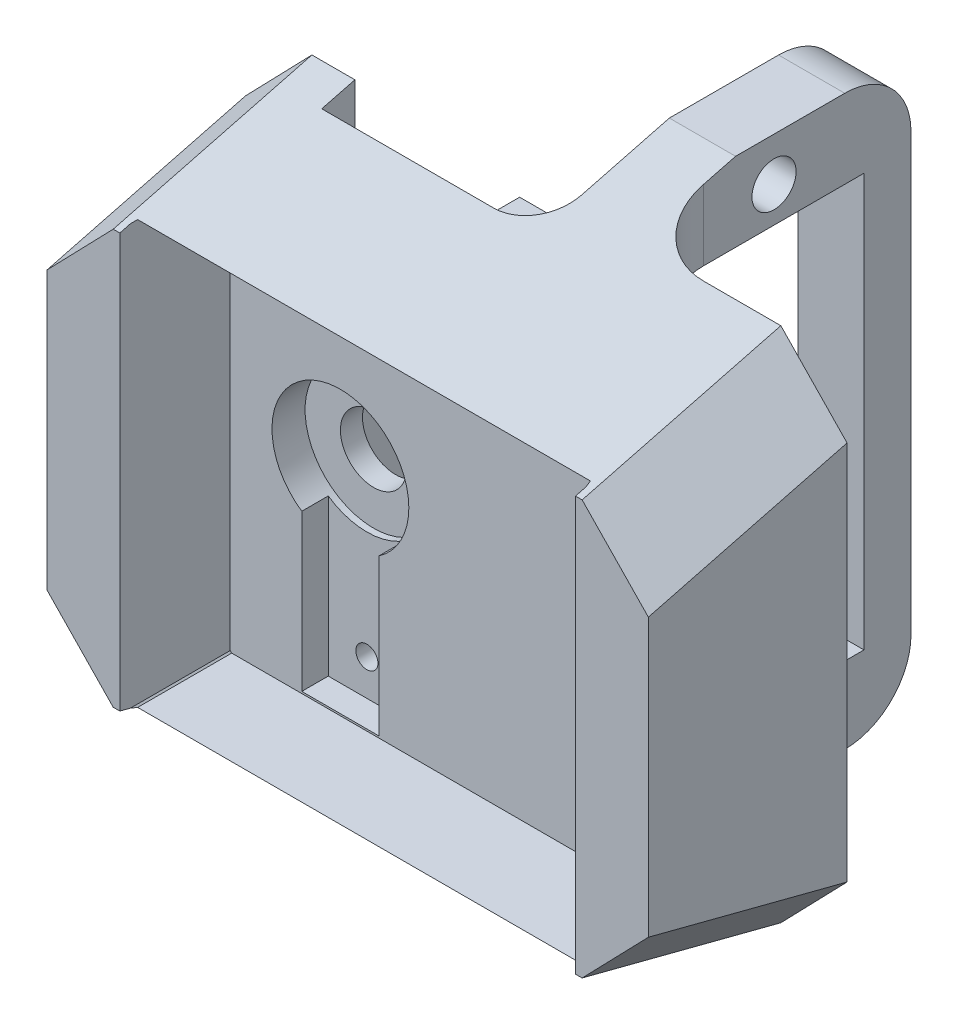
SolidWorks part; units mm, degrees
ref_plane "前视基准面" through (0, 0, 0) normal (0, 0, 1) x (1, 0, 0)
ref_plane "上视基准面" through (0, 0, 0) normal (0, 1, 0) x (1, 0, 0)
ref_plane "右视基准面" through (0, 0, 0) normal (1, 0, 0) x (0, 0, -1)
sketch "Sketch1" plane through (0, 0, 0) normal (1, 0, 0) x (0, 0, -1)
  line L8 (5.3085, 19.1932) -> (-2.8415, 19.1932)
  line L9 (5.3085, 19.1932) -> (5.3085, 0.4932)
  line L10 (5.3085, 0.4932) -> (-2.8415, 0.4932)
  line L11 (-2.8415, 19.1932) -> (-2.8415, 0.4932)
  line L12 (5.3085, 19.1932) -> (-2.8415, 0.4932) construction
  line L13 (-4.9711, 22.7658) -> (7.4381, 22.7658)
  line L14 (-4.9711, 22.7658) -> (-4.9711, -2.9727)
  line L15 (-4.9711, -2.9727) -> (7.4381, -2.9727)
  line L16 (7.4381, 22.7658) -> (7.4381, -2.9727)
  line L17 (5.3085, 0.4932) -> (-2.8415, 19.1932) construction
  line L18 (2.0348, 20.7982) -> (0.4322, 20.7982) construction
  line L19 (2.0348, 20.7982) -> (2.0348, -1.1118) construction
  line L20 (2.0348, -1.1118) -> (0.4322, -1.1118) construction
  line L21 (0.4322, 20.7982) -> (0.4322, -1.1118) construction
  line L22 (2.0348, 20.7982) -> (0.4322, -1.1118) construction
  line L23 (2.0348, -1.1118) -> (0.4322, 20.7982) construction
  circle A4 centre (1.2335, 20.7982) radius 1
  circle A5 centre (1.2335, -1.1118) radius 1
  point P0 (1.2335, 9.8432)
  point P6 (1.2335, 9.8432)
  dimension "D1" = 8.15
  dimension "D2" = 18.7
  dimension "D3" = 21.91
  dimension "D4" = 0
  dimension "D5" = 0
extrude "Boss-Extrude1" add sketch "Sketch1" along normal blind 3
sketch "Sketch15" plane through (0, 0, 4.9711) normal (0, 0, 1) x (1, 0, 0)
  line L0 (3, 22.7658) -> (0, 22.7658) construction
  line L1 (-14.7283, -2.9727) -> (12.5127, -2.9727)
  line L2 (-14.7283, -2.9727) -> (-14.7283, 22.7658)
  line L3 (-14.7283, 22.7658) -> (12.5127, 22.7658)
  line L4 (12.5127, -2.9727) -> (12.5127, 22.7658)
  line L5 (3, -2.9727) -> (0, -2.9727) construction
  dimension "D1" = 0
  dimension "D2" = 0
extrude "Boss-Extrude5" add sketch "Sketch15" along normal blind 4
sketch "Sketch16" plane through (0, 0, 8.9711) normal (0, 0, 1) x (1, 0, 0)
  line L0 (4.7823, 10.0387) -> (3.2978, 10.0387) construction
  circle A0 centre (-6.4376, 10.0387) radius 3.1
  dimension "D1" = 6.2
extrude "Cut-Extrude12" cut sketch "Sketch16" against normal blind 1.5
sketch "Sketch17" plane through (0, 0, 8.9711) normal (0, 0, 1) x (1, 0, 0)
  line L0 (-6.4376, 10.0387) -> (-8.1876, 10.0387)
  line L1 (-8.1876, 19.6653) -> (-4.6876, 19.6653) construction
  line L2 (-8.1876, 19.6653) -> (-8.1876, 0.412) construction
  line L3 (-8.1876, 0.412) -> (-4.6876, 0.412)
  line L4 (-4.6876, 19.6653) -> (-4.6876, 0.412) construction
  line L5 (-8.1876, 19.6653) -> (-4.6876, 0.412) construction
  line L6 (-8.1876, 0.412) -> (-4.6876, 19.6653) construction
  line L7 (-8.1876, 10.0387) -> (-8.1876, 0.412)
  line L8 (-6.4376, 10.0387) -> (-4.6876, 10.0387)
  line L9 (-4.6876, 10.0387) -> (-4.6876, 0.412)
  point P0 (-6.4376, 10.0387)
  dimension "D1" = 3.5
extrude "Cut-Extrude13" cut sketch "Sketch17" against normal blind 1.2
chamfer "Chamfer1" distance 2 angle 45 4 edges at (12.5127, -2.9727, 6.9711) (-14.7283, -2.9727, 6.9711) (-14.7283, 22.7658, 6.9711) (12.5127, 22.7658, 6.9711)
sketch "Sketch18" plane through (0, 0, 7.4711) normal (0, 0, 1) x (1, 0, 0)
  circle A0 centre (-6.4376, 10.0387) radius 1.5
  circle A1 centre (-6.4376, 2.0387) radius 0.5
  dimension "D1" = 8
extrude "Cut-Extrude14" cut sketch "Sketch18" against normal through all both and the other way through all
fillet "Fillet1" radius 3 2 edges at (1.5, -2.9727, -7.4381) (1.5, 22.7658, -7.4381)
fillet "Fillet2" radius 3 1 edges at (3, 9.8966, 4.9711)
sketch "Sketch20" plane through (0, 0, 8.9711) normal (0, 0, 1) x (1, 0, 0)
  line L8 (9.1458, 0.3273) -> (9.2127, 0.3942)
  line L9 (9.1458, 0.3273) -> (9.2127, 0.3942)
  line L10 (9.2127, 19.3989) -> (9.1458, 19.4658)
  line L11 (9.2127, 19.3989) -> (9.1458, 19.4658)
  line L12 (-11.3614, 19.4658) -> (-11.4283, 19.3989)
  line L13 (-11.3614, 19.4658) -> (-11.4283, 19.3989)
  line L14 (-11.4283, 0.3942) -> (-11.3614, 0.3273)
  line L15 (-11.4283, 0.3942) -> (-11.3614, 0.3273)
  line L16 (-12.7283, 22.7658) -> (-14.7283, 20.7658) construction
  line L17 (-12.7283, 22.7658) -> (-14.7283, 20.7658)
  line L18 (-14.7283, 20.7658) -> (-14.7283, -0.9727) construction
  line L19 (-14.7283, 20.7658) -> (-14.7283, -0.9727)
  line L20 (10.5127, 22.7658) -> (-12.7283, 22.7658) construction
  line L21 (12.5127, 20.7658) -> (10.5127, 22.7658) construction
  line L22 (12.5127, -0.9727) -> (12.5127, 20.7658) construction
  line L23 (10.5127, -2.9727) -> (12.5127, -0.9727) construction
  line L24 (-11.3614, 0.3273) -> (9.1458, 0.3273)
  line L26 (9.2127, 0.3942) -> (9.2127, 19.3989)
  line L28 (9.1458, 19.4658) -> (-11.3614, 19.4658)
  line L30 (-11.4283, 19.3989) -> (-11.4283, 0.3942)
  line L32 (-11.3614, 0.3273) -> (9.1458, 0.3273)
  line L34 (9.2127, 0.3942) -> (9.2127, 19.3989)
  line L36 (9.1458, 19.4658) -> (-11.3614, 19.4658)
  line L38 (-11.4283, 19.3989) -> (-11.4283, 0.3942)
  line L40 (-12.7283, -2.9727) -> (10.5127, -2.9727) construction
  line L41 (10.5127, 22.7658) -> (-12.7283, 22.7658)
  line L42 (12.5127, 20.7658) -> (10.5127, 22.7658)
  line L43 (12.5127, -0.9727) -> (12.5127, 20.7658)
  line L44 (10.5127, -2.9727) -> (12.5127, -0.9727)
  line L45 (-12.7283, -2.9727) -> (10.5127, -2.9727)
  line L46 (-14.7283, -0.9727) -> (-12.7283, -2.9727) construction
  line L47 (-14.7283, -0.9727) -> (-12.7283, -2.9727)
  dimension "D1" = 3.3
extrude "Boss-Extrude7" add sketch "Sketch20" along normal blind 5
sketch "Sketch21" plane through (-14.7283, 0, 0) normal (-1, 0, 0) x (0, 0, 1)
  line L0 (4.9711, 9.8966) -> (7.926, 9.8966) construction
  line L2 (0.5086, 22.7658) -> (13.9711, 19.2742)
  line L3 (4.9711, 22.7658) -> (13.9711, 22.7658) construction
  line L4 (13.9711, 20.7658) -> (13.9711, -0.9727) construction
  line L5 (13.9711, 19.2742) -> (13.9711, 24.162)
  line L6 (13.9711, 24.162) -> (0.5086, 24.162)
  line L7 (0.5086, 24.162) -> (0.5086, 22.7658)
  line L8 (0.5086, -4.3689) -> (0.5086, -2.9727)
  line L9 (13.9711, -4.3689) -> (0.5086, -4.3689)
  line L10 (13.9711, 0.5189) -> (13.9711, -4.3689)
  line L11 (0.5086, -2.9727) -> (13.9711, 0.5189)
  line L12 (-4.4381, 22.7658) -> (4.9711, 22.7658) construction
extrude "Cut-Extrude15" cut sketch "Sketch21" against normal through all both and the other way through all
chamfer "Chamfer2" distance 3 angle 45 4 edges at (-14.7283, -0.2269, 11.0955) (12.5127, 20.02, 11.0955) (12.5127, -0.2269, 11.0955) (-14.7283, 20.02, 11.0955)
sketch "Sketch23" plane through (0, 0, 4.9711) normal (0, 0, -1) x (-1, 0, 0)
  circle A0 centre (6.4376, 10.0387) radius 3.3189
  circle A1 centre (6.4376, 2.0387) radius 1.409
extrude "Cut-Extrude17" cut sketch "Sketch23" against normal blind 1
fillet "Fillet4" radius 3 2 edges at (9.2127, 9.8966, 8.9711) (-1.1078, 19.4658, 8.9711)
sketch "Sketch24" plane through (0, 0, 4.9711) normal (0, 0, -1) x (-1, 0, 0)
  line L0 (14.7283, 8.3248) -> (9.7818, 8.3248)
  line L1 (14.7283, 18.5092) -> (14.7283, 1.284) construction
  line L2 (9.7818, 8.3248) -> (9.7818, -1.8153)
  line L3 (11.7283, -1.8153) -> (0, -1.8153) construction
  line L4 (9.7818, -1.8153) -> (11.7283, -1.8153)
  line L5 (11.7283, -1.8153) -> (14.7283, 1.284) construction
  line L6 (11.7283, -1.8153) -> (14.7283, 1.284)
  line L7 (14.7283, 1.284) -> (14.7283, 8.3248)
extrude "Boss-Extrude8" add sketch "Sketch24" along normal up to surface (12.4092 mm away) up to face at (1.5, 9.8966, -7.4381)
sketch "Sketch25" plane through (-14.7283, 0, 0) normal (-1, 0, 0) x (0, 0, 1)
  line L0 (-1.2335, 19.7982) -> (-1.2335, 16.1264) construction
  circle A0 centre (-1.2335, 4.7007) radius 1.5
extrude "Cut-Extrude18" cut sketch "Sketch25" against normal blind 13
sketch "Sketch26" plane through (-14.7283, 0, 0) normal (-1, 0, 0) x (0, 0, 1)
  circle A0 centre (-1.2335, 4.7007) radius 2.992
extrude "Cut-Extrude19" cut sketch "Sketch26" against normal blind 1
fillet "Fillet5" radius 8 1 edges at (-12.255, 8.3248, 4.9711) conic rho 0.35
fillet "Fillet6" radius 4 1 edges at (-10.755, -1.8153, -7.4381)
sketch "Sketch27" plane through (0, 0, 4.9711) normal (0, 0, -1) x (-1, 0, 0)
  line L1 (0, 21.6084) -> (9.7818, 21.6084)
  line L2 (0, 21.6084) -> (0, -1.8153)
  line L3 (0, -1.8153) -> (9.7818, -1.8153)
  line L4 (9.7818, 21.6084) -> (9.7818, -1.8153)
extrude "Cut-Extrude20" cut sketch "Sketch27" against normal blind 1.5
fillet "Fillet7" radius 2 1 edges at (0, 9.8966, 6.4711)
